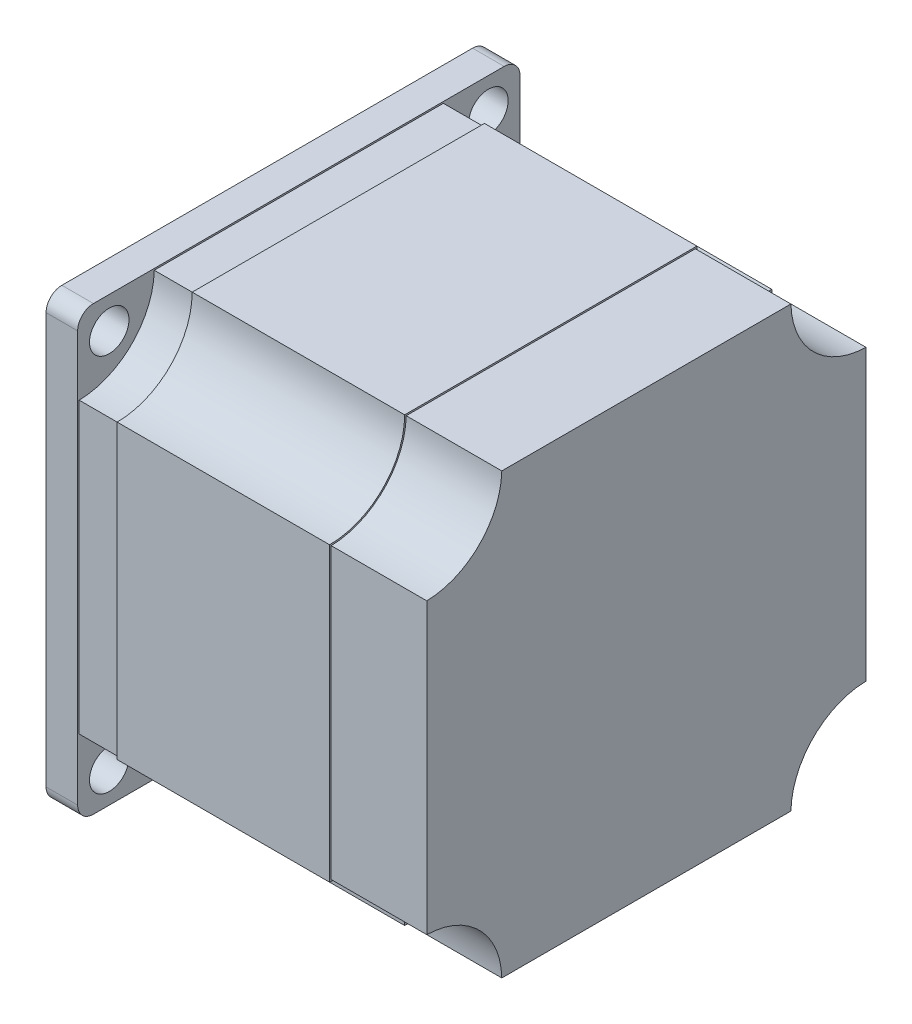
SolidWorks part; units mm, degrees
ref_plane "Front" through (0, 0, 0) normal (0, 0, 1) x (1, 0, 0)
ref_plane "Top" through (0, 0, 0) normal (0, 1, 0) x (1, 0, 0)
ref_plane "Right" through (0, 0, 0) normal (1, 0, 0) x (0, 0, -1)
sketch "Sketch1" plane through (0, 0, 0) normal (1, 0, 0) x (0, 0, -1)
  line L0 (-53.617, 0) -> (72.2837, 0) construction
  line L1 (-18.5, 28) -> (18.5, 28)
  line L2 (-28, 18.5) -> (-28, -18.5)
  line L3 (-18.5, -28) -> (18.5, -28)
  line L4 (28, 18.5) -> (28, -18.5)
  line L5 (-28, 28) -> (28, -28) construction
  line L6 (-28, -28) -> (28, 28) construction
  line L7 (0, 48.9504) -> (0, -61.2624) construction
  arc A0 (18.5, 28) -> (28, 18.5) centre (28, 28) ccw
  arc A1 (28, -18.5) -> (18.5, -28) centre (28, -28) ccw
  arc A2 (-18.5, -28) -> (-28, -18.5) centre (-28, -28) ccw
  arc A3 (-28, 18.5) -> (-18.5, 28) centre (-28, 28) ccw
  circle A4 centre (0, 0) radius 3
  point P0 (0, 0)
  point P19 (0, 0)
  dimension "D1" = 6
  dimension "D2" = 56
  dimension "D4" = 37
  dimension "D6" = 28
  dimension "D7" = 28
  dimension "D3" = 4
extrude "Boss-Extrude1" add sketch "Sketch1" along normal blind 27
sketch "Sketch6" plane through (27, 0, 0) normal (1, 0, 0) x (0, 0, -1)
  line L8 (18.3021, 27.8) -> (-18.3021, 27.8)
  line L9 (-27.8, 18.3021) -> (-27.8, -18.3021)
  line L10 (-18.3021, -27.8) -> (18.3021, -27.8)
  line L11 (27.8, -18.3021) -> (27.8, 18.3021)
  line L12 (18.3021, 27.8) -> (-18.3021, 27.8)
  line L13 (-27.8, 18.3021) -> (-27.8, -18.3021)
  line L14 (-18.3021, -27.8) -> (18.3021, -27.8)
  line L15 (27.8, -18.3021) -> (27.8, 18.3021)
  line L16 (28, -18.5) -> (28, 18.5)
  line L17 (-18.5, -28) -> (18.5, -28)
  line L18 (-28, 18.5) -> (-28, -18.5)
  line L19 (18.5, 28) -> (-18.5, 28)
  line L20 (28, -18.5) -> (28, 18.5)
  line L21 (-18.5, -28) -> (18.5, -28)
  line L22 (-28, 18.5) -> (-28, -18.5)
  line L23 (18.5, 28) -> (-18.5, 28)
  arc A8 (18.3021, 27.8) -> (27.8, 18.3021) centre (28, 28) ccw
  arc A9 (-27.8, 18.3021) -> (-18.3021, 27.8) centre (-28, 28) ccw
  arc A10 (-18.3021, -27.8) -> (-27.8, -18.3021) centre (-28, -28) ccw
  arc A11 (27.8, -18.3021) -> (18.3021, -27.8) centre (28, -28) ccw
  arc A12 (18.3021, 27.8) -> (27.8, 18.3021) centre (28, 28) ccw
  arc A13 (-27.8, 18.3021) -> (-18.3021, 27.8) centre (-28, 28) ccw
  arc A14 (-18.3021, -27.8) -> (-27.8, -18.3021) centre (-28, -28) ccw
  arc A15 (27.8, -18.3021) -> (18.3021, -27.8) centre (28, -28) ccw
  arc A16 (18.5, 28) -> (28, 18.5) centre (28, 28) ccw
  arc A17 (28, -18.5) -> (18.5, -28) centre (28, -28) ccw
  arc A18 (-18.5, -28) -> (-28, -18.5) centre (-28, -28) ccw
  arc A19 (-28, 18.5) -> (-18.5, 28) centre (-28, 28) ccw
  arc A20 (18.5, 28) -> (28, 18.5) centre (28, 28) ccw
  arc A21 (28, -18.5) -> (18.5, -28) centre (28, -28) ccw
  arc A22 (-18.5, -28) -> (-28, -18.5) centre (-28, -28) ccw
  arc A23 (-28, 18.5) -> (-18.5, 28) centre (-28, 28) ccw
  dimension "D1" = 0.2
  dimension "D2" = 0
extrude "Cut-Extrude4" cut sketch "Sketch6" against normal blind 0.1
sketch "Sketch10" plane through (27, 0, 0) normal (1, 0, 0) x (0, 0, -1)
  line L4 (27.8, -18.3021) -> (27.8, 18.3021)
  line L5 (27.8, -18.3021) -> (27.8, 18.3021)
  line L6 (18.3021, 27.8) -> (-18.3021, 27.8)
  line L7 (18.3021, 27.8) -> (-18.3021, 27.8)
  line L12 (-27.8, 18.3021) -> (-27.8, -18.3021)
  line L13 (-27.8, 18.3021) -> (-27.8, -18.3021)
  line L14 (-18.3021, -27.8) -> (18.3021, -27.8)
  line L15 (-18.3021, -27.8) -> (18.3021, -27.8)
  arc A4 (18.3021, 27.8) -> (27.8, 18.3021) centre (28, 28) ccw
  arc A5 (18.3021, 27.8) -> (27.8, 18.3021) centre (28, 28) ccw
  arc A6 (-27.8, 18.3021) -> (-18.3021, 27.8) centre (-28, 28) ccw
  arc A7 (-27.8, 18.3021) -> (-18.3021, 27.8) centre (-28, 28) ccw
  arc A12 (-18.3021, -27.8) -> (-27.8, -18.3021) centre (-28, -28) ccw
  arc A13 (-18.3021, -27.8) -> (-27.8, -18.3021) centre (-28, -28) ccw
  arc A14 (27.8, -18.3021) -> (18.3021, -27.8) centre (28, -28) ccw
  arc A15 (27.8, -18.3021) -> (18.3021, -27.8) centre (28, -28) ccw
  dimension "D1" = 0
extrude "Boss-Extrude4" add sketch "Sketch10" along normal blind 12
sketch "Sketch12" plane through (0, 0, 0) normal (-1, 0, 0) x (0, 0, 1)
  line L4 (-27.8, 18.3021) -> (-27.8, -18.3021)
  line L5 (18.3021, 27.8) -> (-18.3021, 27.8)
  line L6 (27.8, -18.3021) -> (27.8, 18.3021)
  line L7 (-18.3021, -27.8) -> (18.3021, -27.8)
  line L8 (-27.8, 18.3021) -> (-27.8, -18.3021)
  line L9 (18.3021, 27.8) -> (-18.3021, 27.8)
  line L10 (27.8, -18.3021) -> (27.8, 18.3021)
  line L11 (-18.3021, -27.8) -> (18.3021, -27.8)
  arc A4 (-18.3021, -27.8) -> (-27.8, -18.3021) centre (-28, -28) ccw
  arc A5 (-27.8, 18.3021) -> (-18.3021, 27.8) centre (-28, 28) ccw
  arc A6 (18.3021, 27.8) -> (27.8, 18.3021) centre (28, 28) ccw
  arc A7 (27.8, -18.3021) -> (18.3021, -27.8) centre (28, -28) ccw
  arc A8 (-18.3021, -27.8) -> (-27.8, -18.3021) centre (-28, -28) ccw
  arc A9 (-27.8, 18.3021) -> (-18.3021, 27.8) centre (-28, 28) ccw
  arc A10 (18.3021, 27.8) -> (27.8, 18.3021) centre (28, 28) ccw
  arc A11 (27.8, -18.3021) -> (18.3021, -27.8) centre (28, -28) ccw
  dimension "D1" = 0
extrude "Boss-Extrude5" add sketch "Sketch12" along normal blind 5
sketch "Sketch14" plane through (-5, 0, 0) normal (-1, 0, 0) x (0, 0, 1)
  line L1 (-26, 28) -> (26, 28)
  line L2 (-28, 26) -> (-28, -26)
  line L3 (-26, -28) -> (26, -28)
  line L4 (28, 26) -> (28, -26)
  line L5 (-28, 28) -> (28, -28) construction
  line L6 (-28, -28) -> (28, 28) construction
  arc A0 (-28, -26) -> (-26, -28) centre (-26, -26) ccw
  arc A1 (26, -28) -> (28, -26) centre (26, -26) ccw
  arc A2 (28, 26) -> (26, 28) centre (26, 26) ccw
  arc A3 (-28, 26) -> (-26, 28) centre (-26, 26) cw
  circle A5 centre (-24, 24) radius 2.5
  circle A6 centre (24, 24) radius 2.5
  circle A7 centre (24, -24) radius 2.5
  circle A8 centre (-24, -24) radius 2.5
  point P0 (0, 0)
  point P30 (0, 0)
  dimension "D1" = 2
  dimension "D4" = 24
  dimension "D5" = 5
  dimension "D6" = 4
  dimension "D2" = 56
  dimension "D3" = 56
extrude "Boss-Extrude7" add sketch "Sketch14" along normal blind 4
sketch "Sketch15" plane through (-9, 0, 0) normal (-1, 0, 0) x (0, 0, 1)
  circle A0 centre (0, 0) radius 19
  dimension "D1" = 38
extrude "Boss-Extrude8" add sketch "Sketch15" along normal blind 2
sketch "Sketch16" plane through (-11, 0, 0) normal (-1, 0, 0) x (0, 0, 1)
  circle A0 centre (0, 0) radius 3
  dimension "D1" = 6
extrude "Cut-Extrude6" cut sketch "Sketch16" against normal blind 10
